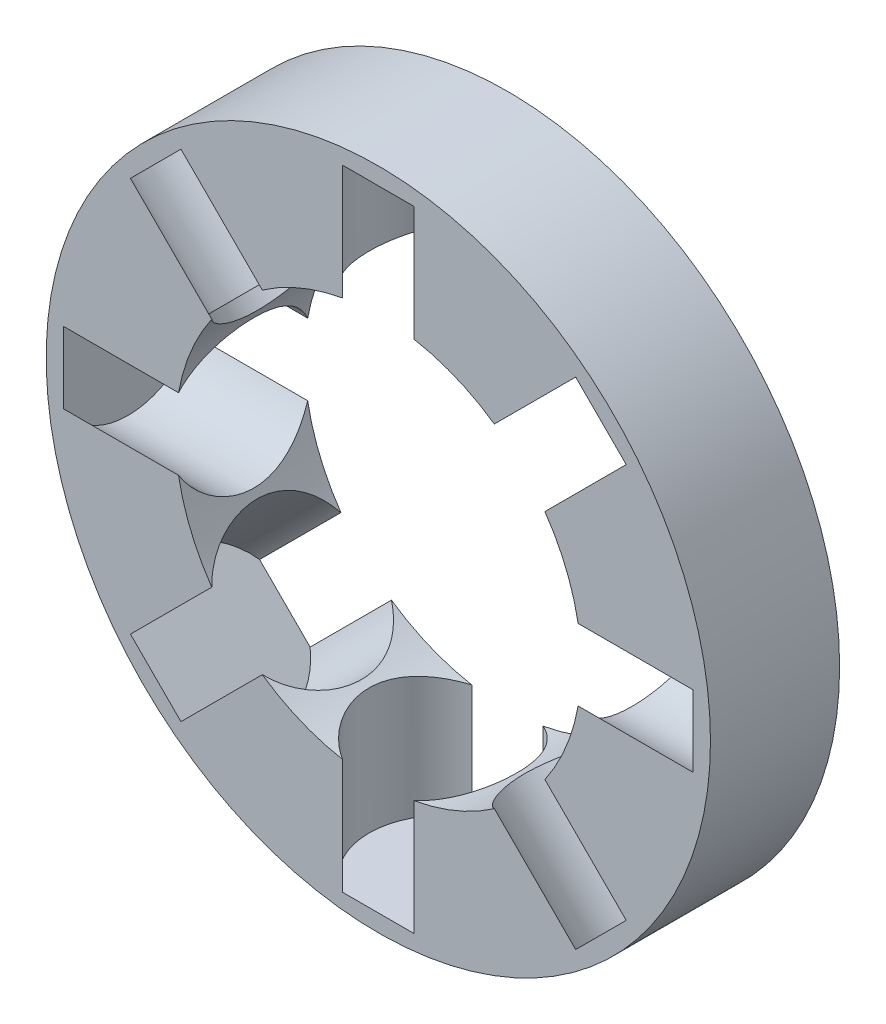
SolidWorks part; units mm, degrees
ref_plane "Top Plane" through (0, 0, 0) normal (0, 0, 1) x (1, 0, 0)
ref_plane "Right Plane" through (0, 0, 0) normal (0, 1, 0) x (1, 0, 0)
ref_plane "Front Plane" through (0, 0, 0) normal (1, 0, 0) x (0, 0, -1)
ref_axis "x-axis" through (-88.99, 0, 0) along (1, 0, 0)
ref_axis "y-axis" through (0, -55, 0) along (0, 1, 0)
ref_axis "z-axis" through (0, 0, 55) along (0, 0, -1)
sketch "Sketch1" plane through (0, 0, 0) normal (0, 0, 1) x (1, 0, 0)
  circle A0 centre (0, 0) radius 11
  circle A1 centre (0, 0) radius 18
  dimension "D1" = 22
  dimension "D2" = 7
extrude "Boss-Extrude1" add sketch "Sketch1" along normal mid plane 7
sketch "Sketch3" plane through (0, 0, 0) normal (0, 0, 1) x (1, 0, 0)
  line L0 (10.1627, -4.2095) -> (10.1627, 4.2095) construction
  line L1 (-10.1627, 4.2095) -> (-10.1627, -4.2095) construction
  line L2 (-10.1627, -4.2095) -> (-4.2095, -10.1627) construction
  line L3 (-4.2095, -10.1627) -> (4.2095, -10.1627) construction
  line L4 (4.2095, -10.1627) -> (10.1627, -4.2095) construction
  line L5 (10.1627, 4.2095) -> (4.2095, 10.1627) construction
  line L6 (4.2095, 10.1627) -> (-4.2095, 10.1627) construction
  line L7 (-4.2095, 10.1627) -> (-10.1627, 4.2095) construction
  line L8 (0, -55) -> (0, 55) construction
  circle A0 centre (0, 0) radius 10.1627 construction
  circle A2 centre (0, 0) radius 11 construction
  point P15 (0, 10.1627)
ref_plane "Plane1" through (-10.1627, 0, 0) normal (1, 0, 0) x (0, 0, -1)
sketch "Sketch4" plane through (-10.1627, 0, 0) normal (1, 0, 0) x (0, 0, -1)
  line L0 (0, 4.2095) -> (0, -4.2095) construction
  circle A0 centre (0, 0) radius 4
  dimension "D1" = 8
extrude "Cut-Extrude1" cut sketch "Sketch4" against normal blind 6.9
pattern_circular "CirPattern1" count 8 over 360 about axis through (0, 0, 3.5) along (0, 0, -1) of "Cut-Extrude1"
sketch "Sketch5" plane through (-12.0651, 12.0651, 0) normal (0.7071, -0.7071, 0) x (0.7071, 0.7071, 0)
  circle A0 centre (0, 0) radius 4
  dimension "D1" = 8
extrude "SpaceClaim for Magnet" add sketch "Sketch5" along normal blind 6
sketch "SpaceClaim for Bearing" plane through (0, 0, 0) normal (0, 0, 1) x (1, 0, 0)
  circle A0 centre (0, 0) radius 11 construction
  dimension "D1" = 22
